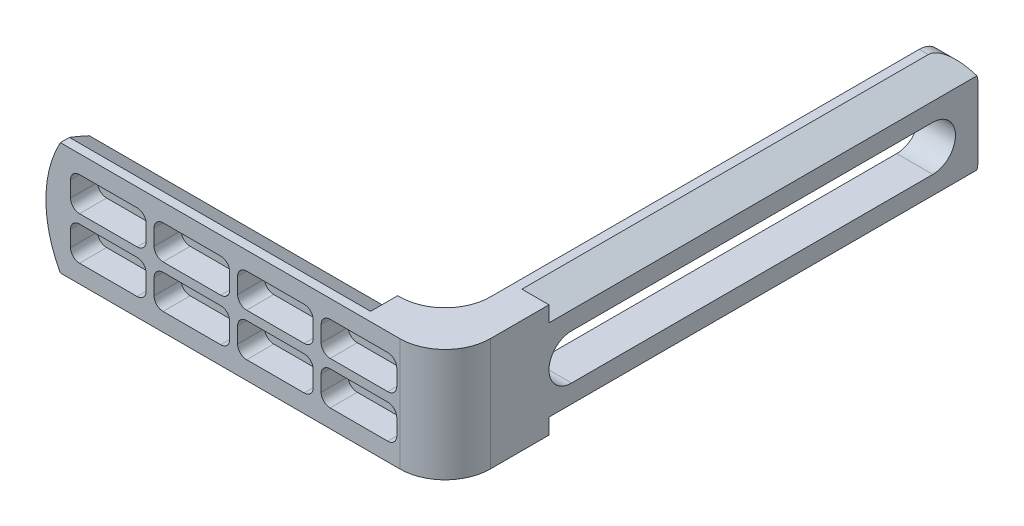
SolidWorks part; units mm, degrees
material "Сплав 2024"
ref_plane "Спереди" through (0, 0, 0) normal (0, 0, 1) x (1, 0, 0)
ref_plane "Сверху" through (0, 0, 0) normal (0, 1, 0) x (1, 0, 0)
ref_plane "Справа" through (0, 0, 0) normal (1, 0, 0) x (0, 0, -1)
sketch "Эскиз1" plane through (0, 0, 0) normal (0, 0, 1) x (1, 0, 0)
  line L1 (0, 0) -> (88.5, 0)
  line L2 (0, 0) -> (0, 25)
  line L3 (0, 25) -> (88.5, 25)
  line L4 (88.5, 0) -> (88.5, 25)
  dimension "D1" = 25
  dimension "D2" = 88.5
extrude "Бобышка-Вытянуть1" add sketch "Эскиз1" along normal blind 8
sketch "Эскиз4" plane through (0, 0, 0) normal (-1, 0, 0) x (0, 0, 1)
  line L0 (6, 0) -> (0, 3.4641)
  line L4 (0, 3.4641) -> (0, 0)
  line L5 (0, 0) -> (6, 0)
  line L6 (0, 12.5) -> (4.1286, 12.5) construction
  line L8 (0, 25) -> (6, 25)
  line L9 (0, 21.5359) -> (0, 25)
  line L11 (6, 25) -> (0, 21.5359)
  line L13 (0, 25) -> (0, 0) construction
  line L14 (8, 0) -> (0, 0) construction
  dimension "D1" = 2
  dimension "D2" = 30
extrude "Вырез-Вытянуть2" cut sketch "Эскиз4" against normal blind 70
sketch "Эскиз9" plane through (0, 0, 8) normal (0, 0, 1) x (1, 0, 0)
  line L0 (0, 12.5) -> (82.9468, 12.5) construction
  line L1 (0, 25) -> (0, 0) construction
  line L3 (5.5532, 13.5) -> (22.3032, 13.5)
  line L4 (5.5532, 13.5) -> (5.5532, 21)
  line L5 (5.5532, 21) -> (22.3032, 21)
  line L6 (22.3032, 13.5) -> (22.3032, 21)
  dimension "D1" = 7.5
  dimension "D2" = 1
  dimension "D3" = 16.75
  dimension "D4" = 5.5532
extrude "Вырез-Вытянуть3" cut sketch "Эскиз9" against normal offset from surface (6 mm away) 2 up to face at (57.125, 12.5, 0)
fillet "Скругление4" radius 2 4 edges at (5.5532, 13.5, 5) (22.3032, 13.5, 5) (22.3032, 21, 5) (5.5532, 21, 5)
pattern_linear "Линейный массив1" count 4 spacing 18.5 along (1, 0, 0) count 2 spacing 9.5 along (0, -1, 0) of "Скругление4", "Вырез-Вытянуть3"
sketch "Эскиз10" plane through (0, 0, 0) normal (0, 0, -1) x (-1, 0, 0)
  line L0 (-70, 0) -> (-88.5, 0) construction
  line L1 (-88.5, 25) -> (-80.5, 25)
  line L2 (-88.5, 25) -> (-88.5, 0)
  line L3 (-88.5, 0) -> (-80.5, 0)
  line L4 (-80.5, 25) -> (-80.5, 0)
  dimension "D1" = 8
extrude "Бобышка-Вытянуть2" add sketch "Эскиз10" along normal blind 110
fillet "Скругление5" radius 10 1 edges at (88.5, 12.5, 8)
fillet "Скругление6" radius 10 1 edges
fillet "Скругление7" radius 5 2 edges at (84.5, 0, -110) (84.5, 25, -110)
sketch "Эскиз11" plane through (0, 0, -110) normal (0, 0, -1) x (-1, 0, 0)
  line L0 (-82.5, 25) -> (-88.5, 25)
  line L2 (-88.5, 25) -> (-88.5, 21.5359)
  line L3 (-88.5, 20) -> (-88.5, 5) construction
  line L4 (-88.5, 21.5359) -> (-82.5, 25)
  line L5 (-80.5, 0) -> (-80.5, 25) construction
  line L6 (-80.5, 12.5) -> (-82.7763, 12.5) construction
  line L7 (-80.5, 5) -> (-80.5, 20) construction
  line L8 (-88.5, 3.4641) -> (-82.5, 0)
  line L9 (-88.5, 0) -> (-88.5, 3.4641)
  line L10 (-82.5, 0) -> (-88.5, 0)
  line L11 (-88.5, 25) -> (-88.5, 20) construction
  dimension "D1" = 2
  dimension "D2" = 30
extrude "Вырез-Вытянуть4" cut sketch "Эскиз11" against normal blind 95
sketch "Эскиз12" plane through (88.5, 0, 0) normal (1, 0, 0) x (0, 0, -1)
  line L0 (110, 12.5) -> (7.3499, 12.5) construction
  line L1 (110, 20) -> (110, 5) construction
  line L2 (20, 12.5) -> (100, 12.5) construction
  line L3 (20, 17.5) -> (100, 17.5)
  line L4 (20, 7.5) -> (100, 7.5)
  arc A0 (20, 17.5) -> (20, 7.5) centre (20, 12.5) ccw
  arc A1 (100, 7.5) -> (100, 17.5) centre (100, 12.5) ccw
  point P6 (60, 12.5)
  dimension "D1" = 10
  dimension "D2" = 80
  dimension "D3" = 10
extrude "Вырез-Вытянуть5" cut sketch "Эскиз12" against normal up to next
sketch "Эскиз13" plane through (0, 0, 0) normal (0, 0, -1) x (-1, 0, 0)
  line L0 (0, 12.5) -> (-5.3037, 12.5) construction
  line L1 (0, 21.5359) -> (0, 3.4641) construction
  line L2 (-3.302, 25) -> (0, 25)
  line L4 (0, 25) -> (0, 0)
  line L5 (0, 0) -> (-3.302, 0)
  line L6 (-70, 0) -> (-70.5, 0) construction
  line L7 (-70, 25) -> (0, 25) construction
  arc A0 (-3.302, 0) -> (-3.302, 25) centre (-26.1, 12.5) ccw
  dimension "D1" = 52
  dimension "D2" = 26.1
extrude "Вырез-Вытянуть7" cut sketch "Эскиз13" against normal up to next
